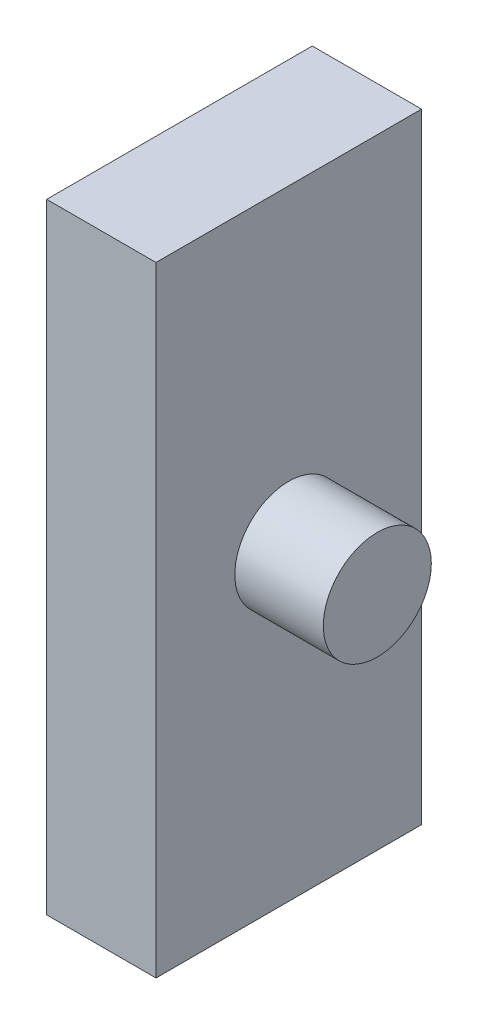
SolidWorks part; units mm, degrees
ref_plane "Front Plane" through (0, 0, 0) normal (0, 0, 1) x (1, 0, 0)
ref_plane "Top Plane" through (0, 0, 0) normal (0, 1, 0) x (1, 0, 0)
ref_plane "Right Plane" through (0, 0, 0) normal (1, 0, 0) x (0, 0, -1)
sketch "Sketch1" plane through (0, 0, 0) normal (1, 0, 0) x (0, 0, -1)
  line L0 (5.8125, 17.5) -> (9.1875, 17.5) construction
  line L1 (5.8125, 26) -> (9.1875, 26)
  line L2 (5.8125, 26) -> (5.8125, 9)
  line L3 (5.8125, 9) -> (9.1875, 9)
  line L4 (9.1875, 26) -> (9.1875, 9)
  line L5 (7.5, 26) -> (7.5, 9) construction
  line L6 (7.5, 35) -> (7.5, 0) construction
  line L15 (0, 35) -> (15, 35)
  line L16 (0, 35) -> (0, 0)
  line L17 (0, 0) -> (15, 0)
  line L18 (15, 35) -> (15, 0)
  line L19 (0, 17.5) -> (15, 17.5) construction
  dimension "D2" = 3.375
  dimension "D3" = 17
  dimension "D4" = 15
  dimension "D5" = 35
extrude "Boss-Extrude1" add sketch "Sketch1" along normal blind 4.175
sketch "Sketch2" plane through (4.175, 0, 0) normal (1, 0, 0) x (0, 0, -1)
  line L1 (0, 35) -> (15, 35)
  line L2 (0, 35) -> (0, 0)
  line L3 (0, 0) -> (15, 0)
  line L4 (15, 35) -> (15, 0)
extrude "Boss-Extrude2" add sketch "Sketch2" along normal blind 2
sketch "Sketch3" plane through (6.175, 0, 0) normal (1, 0, 0) x (0, 0, -1)
  line L0 (7.5, 35) -> (7.5, 0) construction
  line L1 (15, 35) -> (0, 35) construction
  line L2 (0, 0) -> (15, 0) construction
  line L3 (0, 17.5) -> (15, 17.5) construction
  line L4 (0, 35) -> (0, 0) construction
  line L5 (15, 0) -> (15, 35) construction
  circle A0 centre (7.5, 17.5) radius 3.05
  dimension "D1" = 6.1
extrude "Boss-Extrude3" add sketch "Sketch3" along normal blind 5
